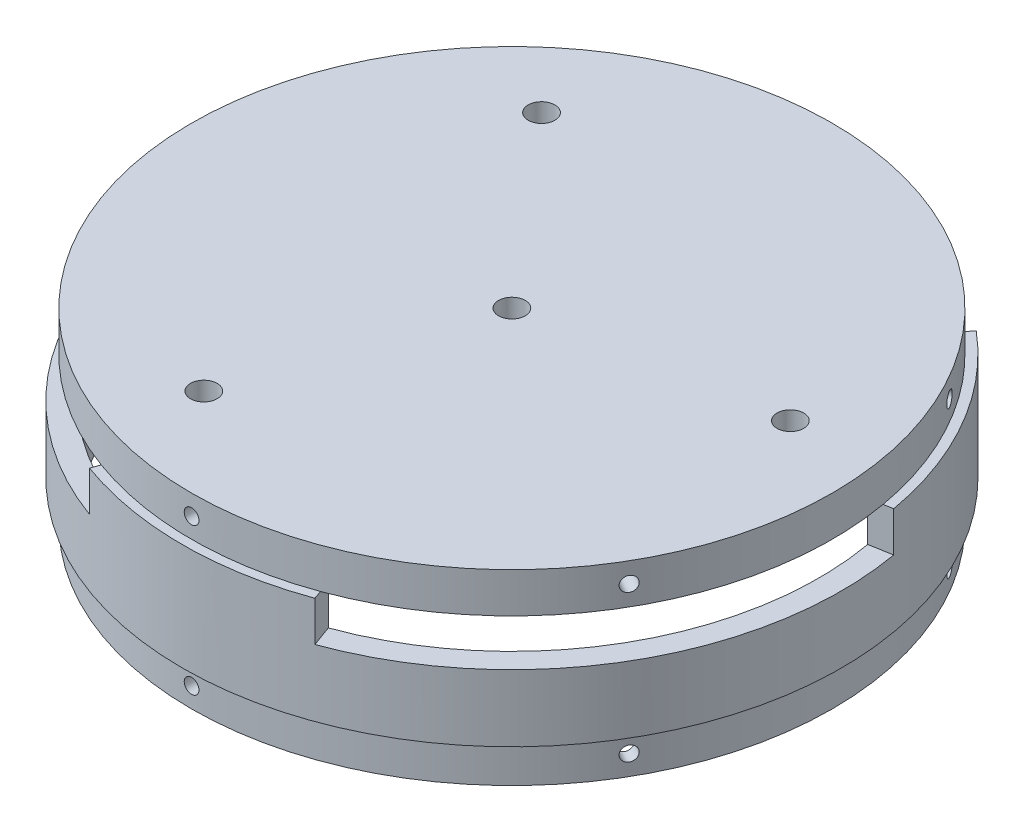
SolidWorks part; units mm, degrees
ref_plane "Front Plane" through (0, 0, 0) normal (0, 0, 1) x (1, 0, 0)
ref_plane "Top Plane" through (0, 0, 0) normal (0, 1, 0) x (1, 0, 0)
ref_plane "Right Plane" through (0, 0, 0) normal (1, 0, 0) x (0, 0, -1)
sketch "Sketch1" plane through (0, 0, 0) normal (0, 1, 0) x (1, 0, 0)
  line L0 (0, 0) -> (-50.3682, 60.0265)
  line L1 (0, 0) -> (50.3682, 60.0265)
  line L2 (0, 0) -> (0, 72.1431) construction
  circle A0 centre (0, 0) radius 78.359
  circle A1 centre (0, 0) radius 76.1746
  circle A2 centre (0, 0) radius 76.1746
  dimension "D1" = 156.718
  dimension "D2" = 152.3492
  dimension "D3" = 152.3492
  dimension "D4" = 80
extrude "Boss-Extrude1" add sketch "Sketch1" along normal blind 25.4 contours L2 A2 L1 A0 | L2 A1 L1 A2 | L2 A2 L1 A1 | L2 A0 L1 A2 | A2 L2 A1 L0 | A0 L2 A2 L0 | A2 L2 A0 L0 | A1 L2 A2 L0 region at (0, 0, 13.3592) region at (-23.5316, 0, -29.974) region at (-33.0764, 0, 70.9325) region at (-48.8794, 0, -59.85)
ref_plane "Plane1" through (0, 12.7, 0) normal (0, 1, 0) x (1, 0, 0)
sketch "Sketch6" plane through (0, 25.4, 0) normal (0, 1, 0) x (1, 0, 0)
  circle A0 centre (0, 0) radius 76.1746
  dimension "D1" = 152.3492
extrude "Boss-Extrude5" add sketch "Sketch6" along normal blind 9.525
sketch "Sketch7" plane through (0, 0, 0) normal (0, -1, 0) x (1, 0, 0)
  circle A0 centre (0, 0) radius 76.1746
  dimension "D1" = 152.3492
extrude "Boss-Extrude6" add sketch "Sketch7" along normal blind 9.525
sketch "Sketch8" plane through (0, -9.525, 0) normal (0, -1, 0) x (1, 0, 0)
  circle A0 centre (0, 0) radius 73.025
  dimension "D1" = 146.05
extrude "Cut-Extrude5" cut sketch "Sketch8" against normal up to surface (34.925 mm away) up to face at (0, 25.4, 76.1746)
ref_plane "Plane2" through (0, 0, -76.1746) normal (0, 0, -1) x (-1, 0, 0)
ref_plane "Plane5" through (0, 25.4, 0) normal (0, 1, 0) x (1, 0, 0)
ref_axis "Axis1" through (0, 0, 0) along (0, 1, 0)
sketch "Sketch3" plane through (0, 0, -76.1746) normal (0, 0, -1) x (-1, 0, 0)
  line L4 (76.1746, 0) -> (-76.1746, 0)
  line L5 (-76.1746, -9.525) -> (76.1746, -9.525)
  line L6 (76.1746, 25.4) -> (-76.1746, 25.4)
  line L7 (76.1746, 34.925) -> (-76.1746, 34.925)
  line L8 (0, 34.925) -> (0, 25.4) construction
  line L9 (0, 0) -> (0, -9.525) construction
  circle A0 centre (0, 30.1625) radius 1.75
  circle A1 centre (0, -4.7625) radius 1.75
  point P12 (0, 30.1625)
  point P13 (0, -4.7625)
  point P14 (-77.5445, 179.1871)
  dimension "D1" = 3.5
extrude "Cut-Extrude2" cut sketch "Sketch3" against normal blind 9.525 contours L8 A0 | L8 A0 | L9 A1 | L9 A1 region at (0, 30.1625, -76.1746) region at (0, -4.7625, -76.1746)
extrude "Cut-Extrude3" cut sketch "Sketch1<7>" against normal blind 9.525 from surface contours L2 A1 L1 A2 | A1 L2 A2 L0 | A2 L2 A0 L0 | L2 A2 L1 A0 region at (-23.5316, 0, -29.974) region at (-48.8794, 0, -59.85) starting at plane "Plane5"
sketch "Sketch1<7>" plane through (0, 0, 0) normal (0, 1, 0) x (1, 0, 0) same geometry as "Sketch1"
pattern_circular "CirPattern2" count 3 over 360 about axis through (0, 0, 0) along (0, 1, 0) of "Cut-Extrude3"
ref_plane "Plane3" through (0, 34.925, 0) normal (0, 1, 0) x (1, 0, 0)
sketch "Sketch4" plane through (0, 34.925, 0) normal (0, 1, 0) x (1, 0, 0)
  circle A0 centre (0, 0) radius 73.025
  dimension "D1" = 146.05
extrude "Boss-Extrude4" add sketch "Sketch4" against normal blind 9.525
pattern_circular "CirPattern3" count 6 over 360 about axis through (0, 0, 0) along (0, 1, 0) of "Cut-Extrude2"
sketch "Sketch9" plane through (0, 34.925, 0) normal (0, 1, 0) x (1, 0, 0)
  line L0 (0, 0) -> (-26.8004, -73.6334) construction
  circle A0 centre (0, 0) radius 3.175
  circle A1 centre (-19.5465, -53.7034) radius 3.175
  circle A2 centre (-36.7353, 43.7794) radius 3.175
  circle A3 centre (56.2818, 9.924) radius 3.175
  point P15 (0, 0)
  dimension "D1" = 6.35
  dimension "D2" = 6.35
  dimension "D3" = 57.15
  dimension "D5" = 3
extrude "Cut-Extrude6" cut sketch "Sketch9" against normal through all
equation "\"AB_Coupler_OD_Length\"= 1in"
equation "\"AB_Coupling_Section_Length\"= 0.375in"
equation "\"AB_Coupler_Length\"= \"AB_Coupler_OD_Length\" + \"AB_Coupling_Section_Length\" * 2"
equation "\"Cutout_Angle\" = 80"
equation "\"AB_Coupler_Num_Screws\"= 6"
equation "\"Num_Cutouts\" = 3"
equation "\"AB_Coupler_OD\"= 6.17in"
equation "\"AB_Coupler_ID\"= 5.75in"
equation "\"AB_Coupler_Surface_Diameter\"= 5.998in"
equation "\"D2@Sketch1\"=\"Bodytube_ID\""
equation "\"AB_Coupling_Screw_Diameter\"= 0.1065in"
equation "\"Aft_Section_Length\"= 40in"
equation "\"Aft_Lower_Length\"= 22in"
equation "\"Aft_Upper_Length\"= \"Aft_Section_Length\" - \"Aft_Lower_Length\" - \"AB_Coupler_OD_Length\""
equation "\"Mid_Coupler_Length\" = 13in"
equation "\"Lead_Screw_Dist\" = 2.25in"
equation "\"Lead_Screw_Diam\" = (27/64)*1in"
equation "\"Lead_Screw_Length\" = (\"Mid_Coupler_Length\" + 2*0.375in + 2*0.5in)"
equation "\"Bodytube_OD\" = 6.17in"
equation "\"Paddle_Pin_Offset\" = .25in"
equation "\"Bodytube_ID\" = 5.998in"
equation "\"Paddle_Pin_Radius\" = 2.25in"
equation "\"D1@Sketch4\"=\"AB_Coupler_ID\""
equation "\"D1@Sketch6\"=\"AB_Coupler_Surface_Diameter\""
equation "\"D1@Boss-Extrude5\"=\"AB_Coupling_Section_Length\""
equation "\"D1@Sketch7\"=\"AB_Coupler_Surface_Diameter\""
equation "\"D1@Boss-Extrude6\"=\"AB_Coupling_Section_Length\""
equation "\"D1@Sketch8\"=\"AB_Coupler_ID\""
equation "\"D3@Sketch9\"=\"Paddle_Pin_Radius\""
